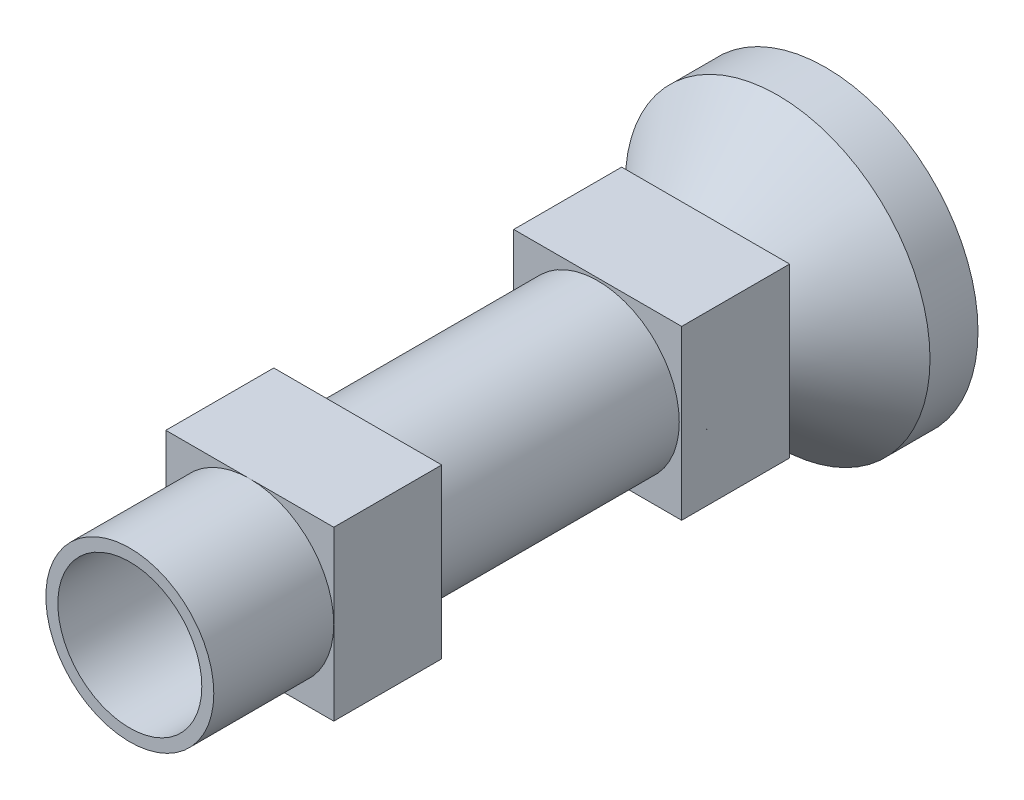
SolidWorks part; units mm, degrees
material "ABS"
ref_plane "正面" through (0, 0, 0) normal (0, 0, 1) x (1, 0, 0)
ref_plane "平面" through (0, 0, 0) normal (0, 1, 0) x (1, 0, 0)
ref_plane "右側面" through (0, 0, 0) normal (1, 0, 0) x (0, 0, -1)
sketch "ｽｹｯﾁ1" plane through (0, 0, 0) normal (0, 0, 1) x (1, 0, 0)
  circle A0 centre (0, 0) radius 3.5 construction
  circle A1 centre (0, 0) radius 6.35
  dimension "D1" = 7
  dimension "D2" = 12.7
ref_plane "平面1" through (0, 0, 5) normal (0, 0, 1) x (1, 0, 0)
sketch "ｽｹｯﾁ2" plane through (0, 0, 5) normal (0, 0, 1) x (1, 0, 0)
  circle A0 centre (0, 0) radius 3.5 construction
  circle A1 centre (0, 0) radius 3.5
ref_plane "平面2" through (0, 0, 29) normal (0, 0, 1) x (1, 0, 0)
ref_plane "平面3" through (0, 0, 24) normal (0, 0, 1) x (1, 0, 0)
sketch "ｽｹｯﾁ5" plane through (0, 0, 29) normal (0, 0, 1) x (1, 0, 0)
  circle A0 centre (0, 0) radius 6.35 construction
  circle A1 centre (0, 0) radius 6.35 construction
  circle A2 centre (0, 0) radius 3.5
  dimension "D1" = 7
extrude "ﾎﾞｽ - 押し出し3" add sketch "ｽｹｯﾁ2" along normal up to surface (19 mm away) contours A1 up to plane "平面3"
extrude "ﾎﾞｽ - 押し出し4" add sketch "ｽｹｯﾁ1" along normal blind 2 separate body
extrude "ﾎﾞｽ - 押し出し5" add sketch "ｽｹｯﾁ5" against normal blind 2
loft "ﾛﾌﾄ1" add section face at (6.35, 0, 2) section face at (3.5, 0, 5) connector at (-0.1759, 6.3476, 2) connector at (-0.0742, 3.4992, 5)
loft "ﾛﾌﾄ2" add section face at (3.5, 0, 24) section face at (3.5, 0, 27) connector at (-0.0749, 3.4992, 24) connector at (-0.0751, 3.4992, 27)
ref_plane "平面5" through (0, 0, 14.5) normal (0, 0, 1) x (1, 0, 0)
ref_plane "平面6" through (0, 0, 15.25) normal (0, 0, 1) x (1, 0, 0)
sketch "ｽｹｯﾁ6" plane through (0, 0, 0) normal (0, 0, -1) x (-1, 0, 0)
  circle A0 centre (0, 0) radius 2.75
  dimension "D1" = 5.5
extrude "ｶｯﾄ - 押し出し1" cut sketch "ｽｹｯﾁ6" against normal blind 3
sketch "ｽｹｯﾁ7" plane through (0, 0, 3) normal (0, 0, -1) x (-1, 0, 0)
  circle A0 centre (0, 0) radius 1.8
  dimension "D1" = 3.6
extrude "ｶｯﾄ - 押し出し2" cut sketch "ｽｹｯﾁ7" against normal through all
sketch "ｽｹｯﾁ8" plane through (0, 0, 29) normal (0, 0, 1) x (1, 0, 0)
  circle A0 centre (0, 0) radius 3
  dimension "D1" = 6
extrude "ｶｯﾄ - 押し出し3" cut sketch "ｽｹｯﾁ8" against normal offset from surface (23 mm away) 3 up to face at (-1.8, 0, 3)
sketch "ｽｹｯﾁ12" plane through (0, 0, 0) normal (0, 0, -1) x (-1, 0, 0)
  line L0 (0, 0) -> (0, 2.75) construction
  line L1 (0, 0) -> (0.3745, 2.7244) construction
  line L2 (0, 0) -> (0.7419, 2.648) construction
  line L3 (0, 0) -> (1.0956, 2.5223) construction
  line L4 (0, 0) -> (1.4289, 2.3497) construction
  line L5 (0, 0) -> (1.7355, 2.1332) construction
  line L6 (0, 0) -> (2.0098, 1.877) construction
  line L7 (0, 0) -> (2.2467, 1.5859) construction
  line L8 (0, 0) -> (2.4417, 1.2652) construction
  line L9 (0, 0) -> (2.5912, 0.9209) construction
  line L10 (0, 0) -> (2.6925, 0.5595) construction
  line L11 (0, 0) -> (2.7436, 0.1877) construction
  line L12 (0, 0) -> (2.7436, -0.1877) construction
  line L13 (0, 0) -> (2.6925, -0.5595) construction
  line L14 (0, 0) -> (2.5912, -0.9209) construction
  line L15 (0, 0) -> (2.4417, -1.2652) construction
  line L16 (0, 0) -> (2.2467, -1.5859) construction
  line L17 (0, 0) -> (2.0098, -1.877) construction
  line L18 (0, 0) -> (1.7355, -2.1332) construction
  line L19 (0, 0) -> (1.4289, -2.3497) construction
  line L20 (0, 0) -> (1.0956, -2.5223) construction
  line L21 (0, 0) -> (0.7419, -2.648) construction
  line L22 (0, 0) -> (0.3745, -2.7244) construction
  line L23 (0, 0) -> (0, -2.75) construction
  line L24 (0, 0) -> (-0.3745, -2.7244) construction
  line L25 (0, 0) -> (-0.7419, -2.648) construction
  line L26 (0, 0) -> (-1.0956, -2.5223) construction
  line L27 (0, 0) -> (-1.4289, -2.3497) construction
  line L28 (0, 0) -> (-1.7355, -2.1332) construction
  line L29 (0, 0) -> (-2.0098, -1.877) construction
  line L30 (0, 0) -> (-2.2467, -1.5859) construction
  line L31 (0, 0) -> (-2.4417, -1.2652) construction
  line L32 (0, 0) -> (-2.5912, -0.9209) construction
  line L33 (0, 0) -> (-2.6925, -0.5595) construction
  line L34 (0, 0) -> (-2.7436, -0.1877) construction
  line L35 (0, 0) -> (-2.7436, 0.1877) construction
  line L36 (0, 0) -> (-2.6925, 0.5595) construction
  line L37 (0, 0) -> (-2.5912, 0.9209) construction
  line L38 (0, 0) -> (-2.4417, 1.2652) construction
  line L39 (0, 0) -> (-2.2467, 1.5859) construction
  line L40 (0, 0) -> (-2.0098, 1.877) construction
  line L41 (0, 0) -> (-1.7355, 2.1332) construction
  line L42 (0, 0) -> (-1.4289, 2.3497) construction
  line L43 (0, 0) -> (-1.0956, 2.5223) construction
  line L44 (0, 0) -> (-0.7419, 2.648) construction
  line L45 (0, 0) -> (-0.3745, 2.7244) construction
  line L46 (0, 0) -> (0.2081, 3.0429) construction
  line L47 (0.2081, 3.0429) -> (-0.0626, 2.7493)
  line L48 (-0.0626, 2.7493) -> (0, 0) construction
  line L49 (0, 0) -> (0.4364, 2.7152) construction
  line L50 (0.4364, 2.7152) -> (0.2081, 3.0429)
  line L51 (1.0214, 2.8739) -> (0.6815, 2.6642)
  line L52 (1.1527, 2.4967) -> (1.0214, 2.8739)
  line L53 (1.7589, 2.4918) -> (1.375, 2.3816)
  line L54 (1.7836, 2.0931) -> (1.7589, 2.4918)
  line L55 (2.3659, 1.9248) -> (1.9666, 1.9223)
  line L56 (2.2822, 1.5343) -> (2.3659, 1.9248)
  line L57 (2.7975, 1.2151) -> (2.4123, 1.3204)
  line L58 (2.6115, 0.8617) -> (2.7975, 1.2151)
  line L59 (3.0216, 0.4153) -> (2.679, 0.6206)
  line L60 (2.7472, 0.1252) -> (3.0216, 0.4153)
  line L61 (3.0216, -0.4153) -> (2.7472, -0.1252)
  line L62 (2.679, -0.6206) -> (3.0216, -0.4153)
  line L63 (2.7975, -1.2151) -> (2.6115, -0.8617)
  line L64 (2.4123, -1.3204) -> (2.7975, -1.2151)
  line L65 (2.3659, -1.9248) -> (2.2822, -1.5343)
  line L66 (1.9666, -1.9223) -> (2.3659, -1.9248)
  line L67 (1.7589, -2.4918) -> (1.7836, -2.0931)
  line L68 (1.375, -2.3816) -> (1.7589, -2.4918)
  line L69 (1.0214, -2.8739) -> (1.1527, -2.4967)
  line L70 (0.6815, -2.6642) -> (1.0214, -2.8739)
  line L71 (0.2081, -3.0429) -> (0.4364, -2.7152)
  line L72 (-0.0626, -2.7493) -> (0.2081, -3.0429)
  line L73 (-0.6205, -2.9862) -> (-0.3123, -2.7322)
  line L74 (-0.802, -2.6304) -> (-0.6205, -2.9862)
  line L75 (-1.4032, -2.708) -> (-1.0379, -2.5466)
  line L76 (-1.482, -2.3165) -> (-1.4032, -2.708)
  line L77 (-2.0818, -2.229) -> (-1.6865, -2.1722)
  line L78 (-2.052, -1.8308) -> (-2.0818, -2.229)
  line L79 (-2.606, -1.5847) -> (-2.21, -1.6366)
  line L80 (-2.4699, -1.2093) -> (-2.606, -1.5847)
  line L81 (-2.9369, -0.8229) -> (-2.5696, -0.9797)
  line L82 (-2.7045, -0.4981) -> (-2.9369, -0.8229)
  line L83 (-3.05, 0) -> (-2.7386, -0.2501)
  line L84 (-2.7386, 0.2501) -> (-3.05, 0)
  line L85 (-2.9369, 0.8229) -> (-2.7045, 0.4981)
  line L86 (-2.5696, 0.9797) -> (-2.9369, 0.8229)
  line L87 (-2.606, 1.5847) -> (-2.4699, 1.2093)
  line L88 (-2.21, 1.6366) -> (-2.606, 1.5847)
  line L89 (-2.0818, 2.229) -> (-2.052, 1.8308)
  line L90 (-1.6865, 2.1722) -> (-2.0818, 2.229)
  line L91 (-1.4032, 2.708) -> (-1.482, 2.3165)
  line L92 (-1.0379, 2.5466) -> (-1.4032, 2.708)
  line L93 (-0.6205, 2.9862) -> (-0.802, 2.6304)
  line L94 (-0.3123, 2.7322) -> (-0.6205, 2.9862)
  circle A0 centre (0, 0) radius 2.75 construction
  circle A1 centre (0, 0) radius 3.05 construction
  arc A2 (0, 2.75) -> (0.3745, 2.7244) centre (0, 0) cw construction
  circle A3 centre (0, 0) radius 2.75 construction
  arc A4 (-0.0626, 2.7493) -> (0.4364, 2.7152) centre (0, 0) cw
  arc A5 (0.6815, 2.6642) -> (1.1527, 2.4967) centre (0, 0) cw
  arc A6 (1.375, 2.3816) -> (1.7836, 2.0931) centre (0, 0) cw
  arc A7 (1.9666, 1.9223) -> (2.2822, 1.5343) centre (0, 0) cw
  arc A8 (2.4123, 1.3204) -> (2.6115, 0.8617) centre (0, 0) cw
  arc A9 (2.679, 0.6206) -> (2.7472, 0.1252) centre (0, 0) cw
  arc A10 (2.7472, -0.1252) -> (2.679, -0.6206) centre (0, 0) cw
  arc A11 (2.6115, -0.8617) -> (2.4123, -1.3204) centre (0, 0) cw
  arc A12 (2.2822, -1.5343) -> (1.9666, -1.9223) centre (0, 0) cw
  arc A13 (1.7836, -2.0931) -> (1.375, -2.3816) centre (0, 0) cw
  arc A14 (1.1527, -2.4967) -> (0.6815, -2.6642) centre (0, 0) cw
  arc A15 (0.4364, -2.7152) -> (-0.0626, -2.7493) centre (0, 0) cw
  arc A16 (-0.3123, -2.7322) -> (-0.802, -2.6304) centre (0, 0) cw
  arc A17 (-1.0379, -2.5466) -> (-1.482, -2.3165) centre (0, 0) cw
  arc A18 (-1.6865, -2.1722) -> (-2.052, -1.8308) centre (0, 0) cw
  arc A19 (-2.21, -1.6366) -> (-2.4699, -1.2093) centre (0, 0) cw
  arc A20 (-2.5696, -0.9797) -> (-2.7045, -0.4981) centre (0, 0) cw
  arc A21 (-2.7386, -0.2501) -> (-2.7386, 0.2501) centre (0, 0) cw
  arc A22 (-2.7045, 0.4981) -> (-2.5696, 0.9797) centre (0, 0) cw
  arc A23 (-2.4699, 1.2093) -> (-2.21, 1.6366) centre (0, 0) cw
  arc A24 (-2.052, 1.8308) -> (-1.6865, 2.1722) centre (0, 0) cw
  arc A25 (-1.482, 2.3165) -> (-1.0379, 2.5466) centre (0, 0) cw
  arc A26 (-0.802, 2.6304) -> (-0.3123, 2.7322) centre (0, 0) cw
  point P53 (0, 0)
  point P54 (0.1877, 2.7436)
  point P56 (0.1877, 2.7436)
  point P129 (0, 0)
  dimension "D2" = 6.1
  dimension "D3" = 10.435
  dimension "D1" = 46
  dimension "D4" = 23
extrude "ｶｯﾄ - 押し出し5" cut sketch "ｽｹｯﾁ12" against normal up to surface (3 mm away) up to face at (-1.8, 0, 3)
sketch "ｽｹｯﾁ14" plane through (0, 0, 24) normal (0, 0, 1) x (1, 0, 0)
  line L1 (3.5, -3.5) -> (-3.5, -3.5)
  line L2 (3.5, -3.5) -> (3.5, 3.5)
  line L3 (3.5, 3.5) -> (-3.5, 3.5)
  line L4 (-3.5, -3.5) -> (-3.5, 3.5)
  line L5 (3.5, -3.5) -> (-3.5, 3.5) construction
  line L6 (3.5, 3.5) -> (-3.5, -3.5) construction
  circle A0 centre (0, 0) radius 3.4
  circle A1 centre (0, 0) radius 3.5 construction
  point P0 (0, 0)
  dimension "D3" = 0.1
  dimension "D1" = 7
  dimension "D2" = 7
extrude "ﾎﾞｽ - 押し出し7" add sketch "ｽｹｯﾁ14" against normal blind 19
sketch "ｽｹｯﾁ16" plane through (0, 0, 14.5) normal (0, 0, 1) x (1, 0, 0)
  line L1 (3.5, -3.5) -> (-3.5, -3.5)
  line L2 (3.5, -3.5) -> (3.5, 3.5)
  line L3 (3.5, 3.5) -> (-3.5, 3.5)
  line L4 (-3.5, -3.5) -> (-3.5, 3.5)
  line L5 (3.5, -3.5) -> (-3.5, 3.5) construction
  line L6 (3.5, 3.5) -> (-3.5, -3.5) construction
  circle A0 centre (0, 0) radius 3.4
  arc A1 (0, 3.5) -> (-3.5, 0) centre (0, 0) ccw construction
  point P0 (0, 0)
  dimension "D1" = 0.1
extrude "ｶｯﾄ - 押し出し6" cut sketch "ｽｹｯﾁ16" against normal blind 5 and the other way blind 5
equation "\"D3@ｽｹｯﾁ12\"=360/23*2/3"
